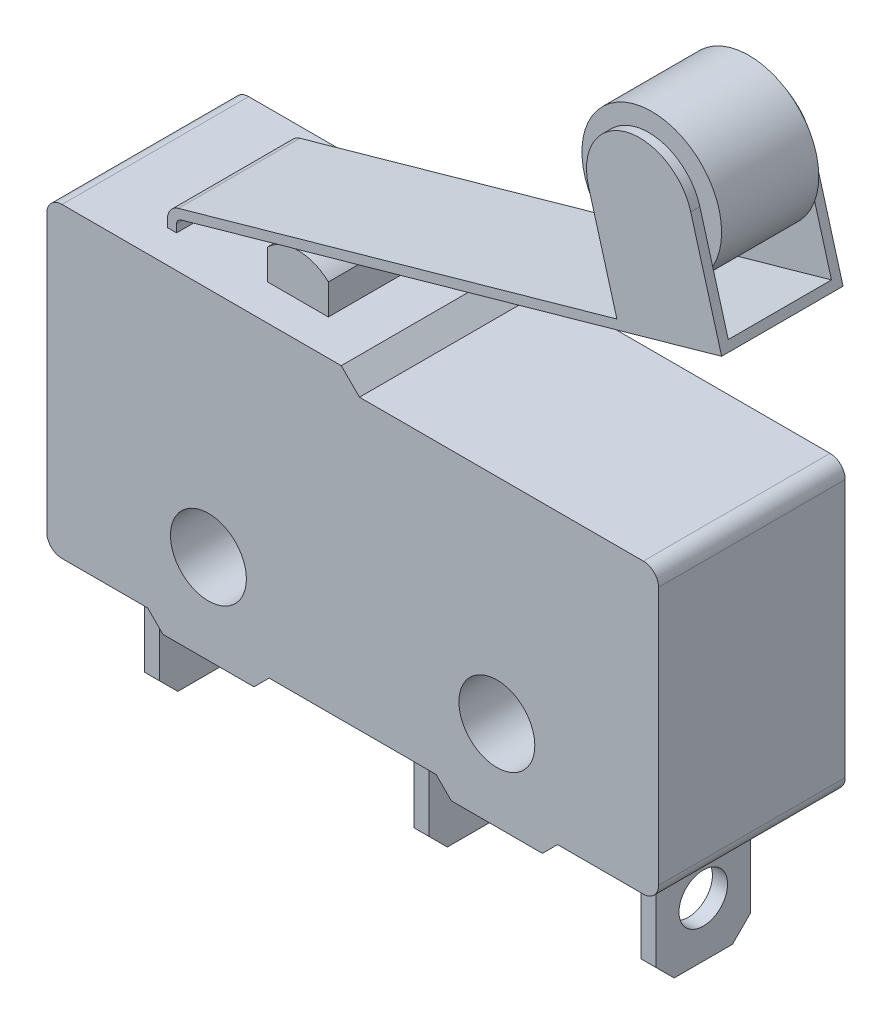
SolidWorks part; units mm, degrees
ref_plane "Alzado" through (0, 0, 0) normal (0, 0, 1) x (1, 0, 0)
ref_plane "Planta" through (0, 0, 0) normal (0, 1, 0) x (1, 0, 0)
ref_plane "Vista lateral" through (0, 0, 0) normal (1, 0, 0) x (0, 0, -1)
sketch "Croquis1" plane through (0, 0, 0) normal (0, 0, 1) x (1, 0, 0)
  line L1 (-10.075, 4.75) -> (10.075, 4.75)
  line L2 (-10.075, 4.75) -> (-10.075, -4.75)
  line L3 (-10.075, -4.75) -> (10.075, -4.75)
  line L4 (10.075, 4.75) -> (10.075, -4.75)
  line L5 (-10.075, 4.75) -> (10.075, -4.75) construction
  line L6 (-10.075, -4.75) -> (10.075, 4.75) construction
  point P0 (0, 0)
  dimension "D1" = 20.15
  dimension "D2" = 9.5
extrude "Saliente-Extruir1" add sketch "Croquis1" along normal mid plane 6.15
sketch "Croquis2" plane through (0, 0, 3.075) normal (0, 0, 1) x (1, 0, 0)
  line L0 (0, 0) -> (0, 50000) construction
  line L1 (10.075, -2.3) -> (-10.075, -2.3) construction
  line L2 (-10.075, 4.75) -> (-10.075, -4.75) construction
  line L3 (-4.75, -3.0785) -> (-4.75, 49996.9215) construction
  line L4 (-6.75, -4.75) -> (-6.25, -5.25)
  line L5 (-10.075, -4.75) -> (10.075, -4.75) construction
  line L6 (-6.25, -5.25) -> (-3.25, -5.25)
  line L7 (-6.75, -4.75) -> (-2.75, -4.75)
  line L8 (-2.75, -4.75) -> (-3.25, -5.25)
  line L9 (-6.75, -4.75) -> (-6.25, -5.25)
  line L10 (-2.75, -4.75) -> (-3.25, -5.25)
  line L11 (4.75, -3.0785) -> (4.75, 49996.9215) construction
  line L12 (2.75, -4.75) -> (3.25, -5.25)
  line L13 (6.75, -4.75) -> (6.25, -5.25)
  line L14 (2.75, -4.75) -> (3.25, -5.25)
  line L15 (6.75, -4.75) -> (2.75, -4.75)
  line L16 (6.25, -5.25) -> (3.25, -5.25)
  line L17 (6.75, -4.75) -> (6.25, -5.25)
  circle A0 centre (-4.75, -2.3) radius 1.25
  circle A1 centre (4.75, -2.3) radius 1.25
  point P20 (-4.75, -5.25)
  point P21 (-4.75, -4.75)
  point P24 (0, -2.3)
  point P30 (4.75, -4.75)
  point P31 (4.75, -5.25)
  line M9 (-10.075, -4.75) -> (10.075, -4.75)
  dimension "D1" = 2.5
  dimension "D2" = 7
  dimension "D5" = 1.7
  dimension "D3" = 4
  dimension "D4" = 45
  dimension "D6" = 0.5
extrude "Saliente-Extruir2" add sketch "Croquis2" against normal up to surface (6.15 mm away) contours L8 L4 L6 M9 | L16 L13 L12 M9 region at (-4.75, -4.9881, 3.075) region at (4.75, -4.9881, 3.075) up to face at (0, 0, -3.075)
extrude "Cortar-Extruir1" cut sketch "Croquis2<3>" against normal up to surface (6.15 mm away) contours A0 | A1 region at (-4.75, -2.3, 3.075) region at (4.75, -2.3, 3.075) up to face at (0, -3.3333, -3.075)
sketch "Croquis2<3>" plane through (0, 0, 3.075) normal (0, 0, 1) x (1, 0, 0) same geometry as "Croquis2"
sketch "Croquis3" plane through (0, 0, 3.075) normal (0, 0, 1) x (1, 0, 0)
  line L0 (-10.075, 4.75) -> (-10.075, 5.35)
  line L1 (-10.075, 5.35) -> (-0.375, 5.35)
  line L2 (-0.375, 5.35) -> (0.225, 4.75)
  line L3 (10.075, 4.75) -> (-10.075, 4.75) construction
  line L4 (0.225, 4.75) -> (-10.075, 4.75)
  dimension "D1" = 45
  dimension "D2" = 10.3
  dimension "D3" = 0.6
extrude "Saliente-Extruir3" add sketch "Croquis3" against normal up to surface (6.15 mm away) up to face at (6, -2.3, -3.075)
sketch "Croquis4" plane through (0, -4.75, 0) normal (0, -1, 0) x (1, 0, 0)
  line L0 (0, 3.075) -> (0, -3.075) construction
  line L1 (-2.75, 3.075) -> (2.75, 3.075) construction
  line L2 (-2.75, -3.075) -> (2.75, -3.075) construction
  line L3 (10.075, 3.075) -> (10.075, -3.075) construction
  line L4 (7.975, -1.56) -> (8.475, -1.56)
  line L5 (7.975, -1.56) -> (7.975, 1.56)
  line L6 (7.975, 1.56) -> (8.475, 1.56)
  line L7 (8.475, -1.56) -> (8.475, 1.56)
  line L8 (7.975, -1.56) -> (8.475, 1.56) construction
  line L9 (7.975, 1.56) -> (8.475, -1.56) construction
  line L10 (10.075, 0) -> (-10.075, 0) construction
  line L11 (-10.075, 3.075) -> (-10.075, -3.075) construction
  line L13 (-8.375, -1.56) -> (-7.875, -1.56)
  line L14 (-8.375, -1.56) -> (-8.375, 1.56)
  line L15 (-8.375, 1.56) -> (-7.875, 1.56)
  line L16 (-7.875, -1.56) -> (-7.875, 1.56)
  line L17 (-8.375, -1.56) -> (-7.875, 1.56) construction
  line L18 (-8.375, 1.56) -> (-7.875, -1.56) construction
  line L19 (0.505, -1.56) -> (1.005, -1.56)
  line L20 (0.505, -1.56) -> (0.505, 1.56)
  line L21 (0.505, 1.56) -> (1.005, 1.56)
  line L22 (1.005, -1.56) -> (1.005, 1.56)
  line L23 (0.505, -1.56) -> (1.005, 1.56) construction
  line L24 (0.505, 1.56) -> (1.005, -1.56) construction
  point P6 (8.225, 0)
  point P18 (8.225, 1.56)
  point P19 (8.225, -1.56)
  point P20 (-8.125, 0)
  point P26 (0.755, 0)
  dimension "D1" = 1.6
  dimension "D2" = 0.5
  dimension "D3" = 3.12
  dimension "D4" = 1.7
  dimension "D5" = 0.5
  dimension "D6" = 8.38
  dimension "D7" = 0.5
extrude "Saliente-Extruir4" add sketch "Croquis4" along normal blind 4
sketch "Croquis5" plane through (-8.375, 0, 0) normal (-1, 0, 0) x (0, 0, 1)
  line L0 (0, -8.75) -> (0, -4.75) construction
  line L1 (1.56, -8.75) -> (-1.56, -8.75) construction
  line L2 (3.075, -4.75) -> (-3.075, -4.75) construction
  line L3 (-1.56, -8.15) -> (-0.96, -8.75)
  line L4 (-1.56, -8.75) -> (-1.56, -4.75) construction
  line L5 (-0.96, -8.75) -> (-1.56, -8.75)
  line L6 (-1.56, -8.75) -> (-1.56, -8.15)
  line L7 (1.56, -8.75) -> (1.56, -8.15)
  line L8 (0.96, -8.75) -> (1.56, -8.75)
  line L9 (1.56, -8.15) -> (0.96, -8.75)
  circle A0 centre (0, -6.95) radius 0.8
  dimension "D3" = 1.6
  dimension "D1" = 45
  dimension "D2" = 0.6
  dimension "D4" = 1
extrude "Cortar-Extruir2" cut sketch "Croquis5" against normal through all
fillet "Redondeo1" radius 0.5 4 edges at (-10.075, -4.75, 0) (10.075, -4.75, 0) (10.075, 4.75, 0) (-10.075, 5.35, 0)
sketch "Croquis6" plane through (0, 0, 0) normal (0, 0, 1) x (1, 0, 0)
  line L0 (-0.375, 5.35) -> (-9.575, 5.35) construction
  line L1 (-1.975, 5.35) -> (-3.975, 5.35)
  line L2 (-1.975, 5.35) -> (-1.975, 6.35)
  line L3 (-1.975, 6.35) -> (-3.975, 6.35)
  line L4 (-3.975, 5.35) -> (-3.975, 6.35)
  line L5 (-10.075, 4.85) -> (-10.075, -4.25) construction
  arc A0 (-3.975, 6.35) -> (-1.975, 6.35) centre (-2.975, 5.3) cw
  point P9 (-2.975, 6.75)
  dimension "D3" = 1.4
  dimension "D1" = 1
  dimension "D2" = 6.1
  dimension "D4" = 2
extrude "Saliente-Extruir5" add sketch "Croquis6" along normal mid plane 3.8 contours A0 L3 | L4 L1 L2 L3 region at (-2.975, 5.85, 0) region at (-2.975, 6.5121, 0)
sketch "Croquis7" plane through (0, 0, 0) normal (0, 0, 1) x (1, 0, 0)
  line L0 (-6.875, 5.35) -> (-6.875, 5.6)
  line L1 (-0.375, 5.35) -> (-9.575, 5.35) construction
  line L2 (-6.7292, 5.7925) -> (11.0788, 10.8051)
  line L3 (-10.075, 4.85) -> (-10.075, -4.25) construction
  line L4 (0.225, 4.75) -> (0.225, 7.75) construction
  line L5 (-7.175, 5.35) -> (-7.175, 5.6)
  line L6 (-6.8105, 6.0813) -> (10.9975, 11.0939)
  line L7 (-7.175, 5.35) -> (-6.875, 5.35)
  line L8 (11.0788, 10.8051) -> (10.9975, 11.0939)
  line L9 (10.9975, 11.0939) -> (10.9236, 11.2188)
  arc A0 (-6.875, 5.6) -> (-6.7292, 5.7925) centre (-6.675, 5.6) cw
  arc A2 (-7.175, 5.6) -> (-6.8105, 6.0813) centre (-6.675, 5.6) cw
  dimension "D1" = 3.2
  dimension "D4" = 0.2
  dimension "D2" = 18.5
  dimension "D3" = 3
  dimension "D6" = 0.25
  dimension "D5" = 0.3
extrude "Saliente-Extruir7" add sketch "Croquis7" along normal mid plane 4 contours L8 L2 A0 L0 L7 L5 A2 L6
sketch "Croquis8" plane through (0, 0, 2) normal (0, 0, 1) x (1, 0, 0)
  line L0 (10.9975, 11.0939) -> (7.6284, 10.1456)
  line L1 (-6.8105, 6.0813) -> (10.9975, 11.0939) construction
  line L2 (7.6284, 10.1456) -> (6.6936, 13.4665)
  line L3 (6.6936, 13.4665) -> (11.372, 14.7834) construction
  line L4 (10.0627, 14.4149) -> (10.9975, 11.0939)
  line L5 (-6.7292, 5.7925) -> (11.0788, 10.8051) construction
  arc A0 (10.0627, 14.4149) -> (6.6936, 13.4665) centre (8.3782, 13.9407) ccw
  dimension "D1" = 5.5
  dimension "D2" = 3.5
extrude "Saliente-Extruir8" add sketch "Croquis8" against normal blind 0.3
mirror "Simetría1" about plane through (0, 0, 0) normal (0, 0, 1) of "Saliente-Extruir8"
sketch "Croquis9" plane through (0, 0, 0) normal (0, 0, 1) x (1, 0, 0)
  circle A0 centre (8.3782, 13.9407) radius 2.3
  dimension "D1" = 4.6
extrude "Saliente-Extruir9" add sketch "Croquis9" along normal mid plane 3.2
